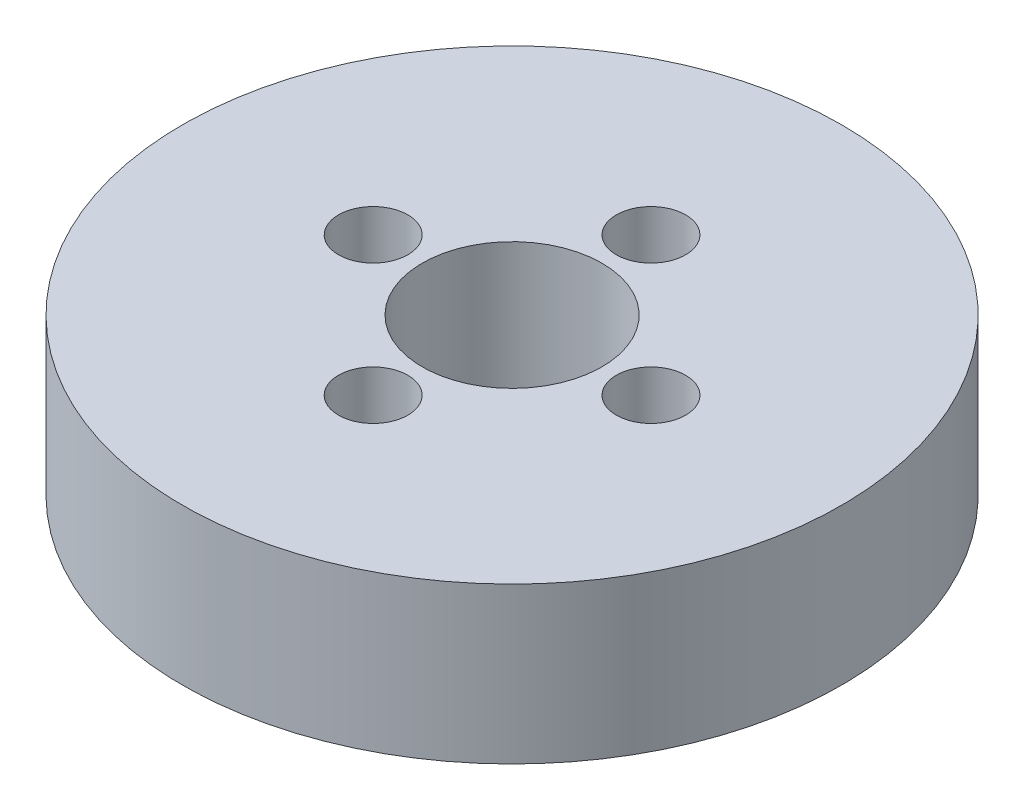
SolidWorks part; units mm, degrees
ref_plane "Front Plane" through (0, 0, 0) normal (0, 0, 1) x (1, 0, 0)
ref_plane "Top Plane" through (0, 0, 0) normal (0, 1, 0) x (1, 0, 0)
ref_plane "Right Plane" through (0, 0, 0) normal (1, 0, 0) x (0, 0, -1)
sketch "Sketch1" plane through (0, 0, 0) normal (0, 1, 0) x (1, 0, 0)
  circle A0 centre (0, 0) radius 55
  dimension "FLANGE_OD" = 110
extrude "Boss-Extrude1" add sketch "Sketch1" along normal blind 26
sketch "Sketch2" plane through (0, 0, 0) normal (0, 1, 0) x (1, 0, 0)
  circle A0 centre (0, 0) radius 15
  dimension "BORE_D" = 30
extrude "Cut-Extrude1" cut sketch "Sketch2" along normal through all
sketch "Sketch3" plane through (0, 26, 0) normal (0, 1, 0) x (1, 0, 0)
  circle A0 centre (0, 0) radius 23.1811 construction
  circle A1 centre (-23.1811, 0) radius 5.7819
  dimension "BOLT_D" = 11.5638
  dimension "BOLT_PCD" = 46.3623
extrude "Cut-Extrude2" cut sketch "Sketch3" against normal blind 24.4359
pattern_circular "CirPattern1" count 4 over 360 about axis through (0, 0, 0) along (0, 1, 0) of "Cut-Extrude2"
